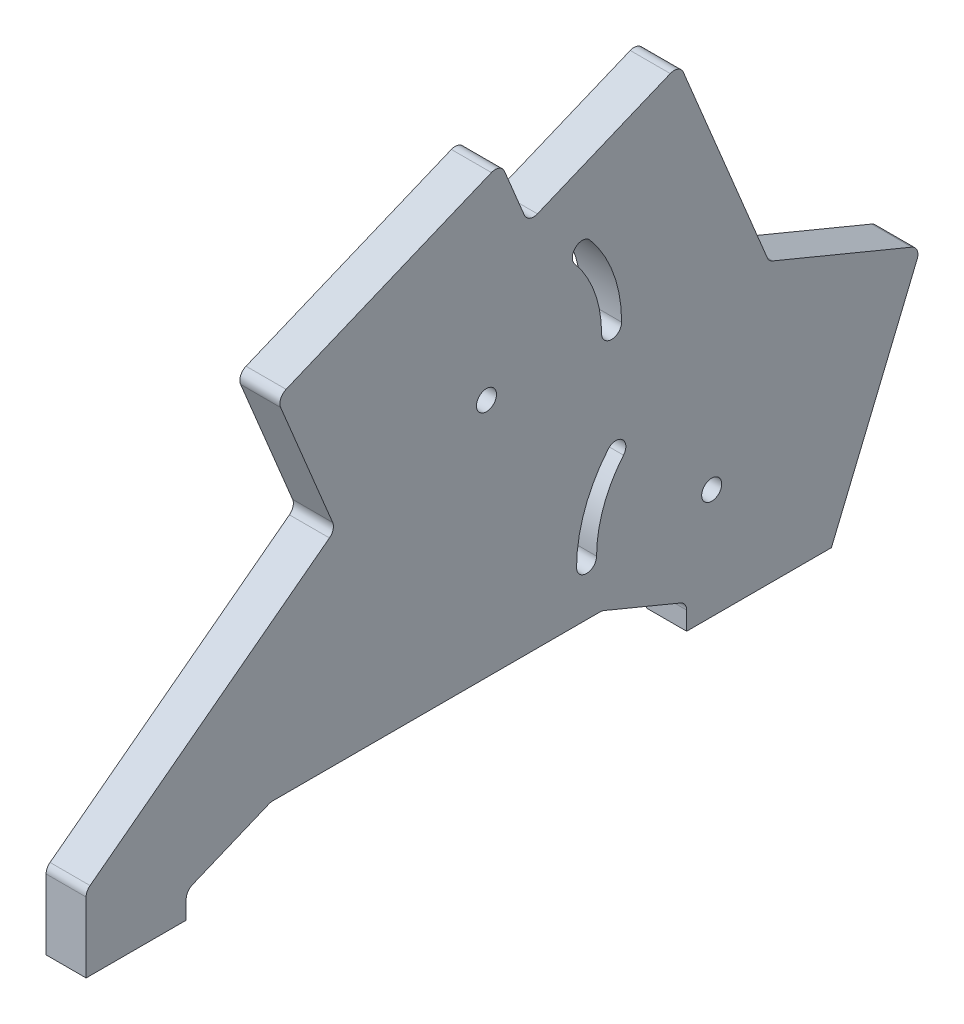
SolidWorks part; units mm, degrees
material "PMMA"
ref_plane "Front Plane" through (0, 0, 0) normal (0, 0, 1) x (1, 0, 0)
ref_plane "Top Plane" through (0, 0, 0) normal (0, 1, 0) x (1, 0, 0)
ref_plane "Right Plane" through (0, 0, 0) normal (1, 0, 0) x (0, 0, -1)
sketch "Sketch1" plane through (0, 0, 0) normal (1, 0, 0) x (0, 0, -1)
  line L0 (0, 0) -> (0, 15)
  line L1 (38.8897, 80.8553) -> (54.5797, 42.9762) construction
  line L2 (38.8897, 80.8553) -> (112.8001, 111.47) construction
  line L3 (54.5797, 42.9762) -> (128.4901, 73.5909) construction
  line L5 (112.8001, 111.47) -> (128.4901, 73.5909) construction
  line L6 (20, 5) -> (20, 0)
  line L7 (0, 0) -> (20, 0)
  line L10 (80, 60) -> (105, 60) construction
  line L11 (99.1511, 76.0697) -> (80, 60) construction
  line L12 (100, 22) -> (125, 22) construction
  line L13 (125, 22) -> (105.8489, 38.0697) construction
  line L14 (166.1103, 42.8553) -> (150.4203, 4.9762) construction
  line L15 (166.1103, 42.8553) -> (92.1999, 73.47) construction
  line L16 (150.4203, 4.9762) -> (76.5099, 35.5909) construction
  line L17 (92.1999, 73.47) -> (76.5099, 35.5909) construction
  line L19 (166.8247, 43.2195) -> (136.4285, 55.81)
  line L20 (38.1102, 81.1261) -> (82.8344, 99.6514)
  line L21 (82.8344, 99.6514) -> (88.3305, 86.3826)
  line L22 (38.1102, 81.1261) -> (49.8545, 52.7728)
  line L23 (49.8545, 52.7728) -> (0, 15)
  line L24 (88.3305, 86.3826) -> (118.5757, 98.9106)
  line L25 (118.5757, 98.9106) -> (136.4285, 55.81)
  line L43 (148.9226, 0) -> (120, 0)
  line L56 (120, 5) -> (120, 0)
  line L58 (20, 5) -> (36.8995, 12)
  line L59 (36.8995, 12) -> (103.1005, 12)
  line L60 (103.1005, 12) -> (120, 5)
  line L61 (148.9226, 0) -> (166.8247, 43.2195)
  line L63 (174.6584, 100) -> (-14.1241, 100) construction
  circle A0 centre (80, 60) radius 2
  circle A1 centre (125, 22) radius 2
  arc A2 (99.1511, 76.0697) -> (105, 60) centre (80, 60) cw construction
  arc A3 (107, 60) -> (100.6832, 77.3553) centre (80, 60) ccw
  arc A4 (103, 60) -> (97.619, 74.7841) centre (80, 60) ccw
  arc A5 (103, 60) -> (107, 60) centre (105, 60) ccw
  arc A6 (100.6832, 77.3553) -> (97.619, 74.7841) centre (99.1511, 76.0697) ccw
  arc A7 (105.8489, 38.0697) -> (100, 22) centre (125, 22) ccw construction
  arc A8 (104.3168, 39.3553) -> (98, 22) centre (125, 22) ccw
  arc A9 (107.381, 36.7841) -> (102, 22) centre (125, 22) ccw
  arc A10 (107.381, 36.7841) -> (104.3168, 39.3553) centre (105.8489, 38.0697) ccw
  arc A11 (98, 22) -> (102, 22) centre (100, 22) ccw
  point P17 (103.4923, 68.5505)
  point P22 (101.5077, 30.5505)
  dimension "D1" = 4
  dimension "D3" = 2
  dimension "D8" = 15
  dimension "D11" = 22
  dimension "D12" = 80
  dimension "D14" = 10
  dimension "D17" = 6
  dimension "D21" = 30
  dimension "D22" = 35
  dimension "D23" = 80
  dimension "D18" = 6
  dimension "D29" = 60
  dimension "D2" = 25
  dimension "D4" = 25
  dimension "D5" = 40
  dimension "D6" = 40
  dimension "D7" = 125
  dimension "D9" = 20
  dimension "D10" = 100
  dimension "D13" = 5
  dimension "D20" = 30
  dimension "D31" = 22.5
  dimension "D32" = 100
  dimension "D33" = 22.5
extrude "Boss-Extrude1" add sketch "Sketch1" along normal blind 8
fillet "Fillet1" radius 2 12 edges at (4, 12, -36.8995) (4, 5, -20) (4, 12, -103.1005) (4, 43.2195, -166.8247) (4, 55.81, -136.4285) (4, 98.9106, -118.5757) (4, 86.3826, -88.3305) (4, 99.6514, -82.8344) (4, 81.1261, -38.1102) (4, 52.7728, -49.8545) (4, 15, 0) (4, 5, -120)
hole_wizard "Tap Drill for M3 Tap1" positions "Sketch3" profile "Sketch2" hole size "M3" standard "ISO"
sketch "Sketch3" plane through (0, 0, 0) normal (0, -1, 0) x (-1, 0, 0)
  line L0 (-8, 20) -> (0, 20) construction
  line L1 (0, 0) -> (0, 20) construction
  line L2 (-8, 120) -> (0, 120) construction
  point P0 (-4, 10)
  point P2 (-4, 130)
  dimension "D1" = 10
  dimension "D2" = 4
  dimension "D3" = 10
sketch "Sketch2" plane through (4, 0, -10) normal (1, 0, 0) x (0, 0, -1)
  line L0 (0, 0) -> (0, 10.7511)
  line L1 (0, 10.7511) -> (1.25, 10)
  line L2 (1.25, 10) -> (1.25, 0)
  line L5 (1.25, 0) -> (0, 0)
  line L10 (0, 10.7511) -> (-1.25, 10) construction
  line L11 (0, -6.35) -> (0, 107.95) construction
  dimension "Hole Dia." = 2.5
  dimension "Hole Depth" = 10
  dimension "Drill Angle" = 118
equation "\"ˇ35\"=76.24"
